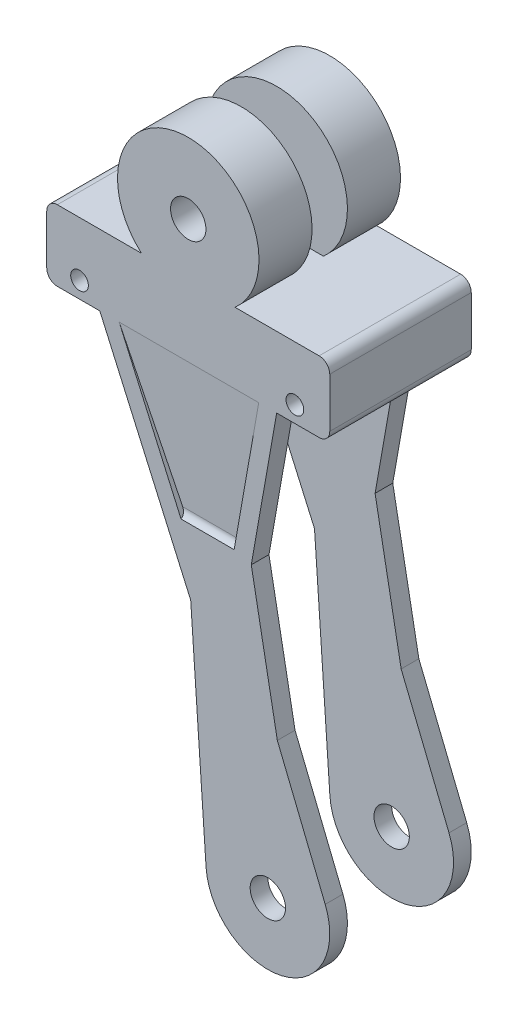
SolidWorks part; units mm, degrees
material "Titanio Ti-8Al-1Mo-1V"
ref_plane "Alzado" through (0, 0, 0) normal (0, 0, 1) x (1, 0, 0)
ref_plane "Planta" through (0, 0, 0) normal (0, 1, 0) x (1, 0, 0)
ref_plane "Vista lateral" through (0, 0, 0) normal (1, 0, 0) x (0, 0, -1)
other "Centro de masa"
sketch "Croquis1" plane through (0, 0, 0) normal (0, 0, 1) x (1, 0, 0)
  line L1 (-37, 0) -> (37, 0)
  line L2 (-40, -3) -> (-40, -17)
  line L3 (-37, -20) -> (37, -20)
  line L4 (40, -3) -> (40, -17)
  arc A0 (37, 0) -> (40, -3) centre (37, -3) cw
  arc A1 (37, -20) -> (40, -17) centre (37, -17) ccw
  arc A2 (-40, -17) -> (-37, -20) centre (-37, -17) ccw
  arc A3 (-37, 0) -> (-40, -3) centre (-37, -3) ccw
  point P6 (40, 0)
  point P9 (40, -20)
  point P14 (-40, 0)
  dimension "D3" = 3
  dimension "D1" = 80
  dimension "D2" = 20
extrude "Saliente-Extruir1" add sketch "Croquis1" along normal blind 40
sketch "Croquis2" plane through (0, 0, 40) normal (0, 0, 1) x (1, 0, 0)
  line L0 (0, -20) -> (22.5, -140) construction
  line L1 (-37, -20) -> (37, -20) construction
  line L2 (40, -17) -> (40, -3) construction
  line L3 (-25, -20) -> (0.6923, -77.9551)
  line L4 (0.6923, -77.9551) -> (5.0412, -141.2005)
  line L5 (-25, -20) -> (0, -20)
  line L6 (0, -20) -> (25, -20)
  line L7 (25.1863, -100.0643) -> (17.8148, -60.7494)
  line L8 (25.1863, -100.0643) -> (38.7168, -133.4223)
  line L9 (0.6923, -77.9551) -> (10.521, -76.1122) construction
  line L10 (17.8148, -60.7494) -> (25, -20)
  arc A0 (5.0412, -141.2005) -> (38.7168, -133.4223) centre (22.5, -140) ccw
  circle A1 centre (22.5, -140) radius 5
  line M7 (-37, -20) -> (37, -20)
  dimension "D2" = 35
  dimension "D8" = 10
  dimension "D1" = 120
  dimension "D3" = 25
  dimension "D4" = 10
  dimension "D5" = 40
  dimension "D6" = 10
  dimension "D7" = 80
extrude "Saliente-Extruir2" add sketch "Croquis2" against normal blind 5 contours L0 L3 L9 M7 | L0 A1 L9 L4 A0 L8 L7 L10 M7 region at (11.0487, -83.3083, 40)
extrude "Saliente-Extruir3" add sketch "Croquis2<4>" along normal blind 5 from surface starting at face at (0, -10, 0)
sketch "Croquis2<4>" plane through (0, 0, 40) normal (0, 0, 1) x (1, 0, 0) same geometry as "Croquis2"
ref_plane "Plano2" through (0, -1.4195, 40.6488) normal (0, -0.0349, 0.9994) x (1, 0, 0)
sketch "Croquis3" plane through (0, -1.4195, 40.6488) normal (0, -0.0349, 0.9994) x (1, 0, 0)
  line L0 (-19.5302, -18.5918) -> (19.9228, -18.5918)
  line L1 (19.9228, -18.5918) -> (12.9644, -58.0309)
  line L2 (12.9644, -58.0309) -> (-2.0356, -58.0309)
  line L3 (-2.0356, -58.0309) -> (-19.5302, -18.5918)
  line L4 (-25, -18.5918) -> (0.6923, -76.5117) construction
  line L5 (17.8148, -59.3164) -> (25, -18.5918) construction
  line L6 (25, -18.5918) -> (37, -18.5918) construction
  dimension "D1" = 5
  dimension "D2" = 5
  dimension "D3" = 15
extrude "Cortar-Extruir1" cut sketch "Croquis3" along normal through all
fillet "Redondeo5" radius 2 1 edges at (5.4644, -59.415, 38.6236)
ref_plane "Plano3" through (0, 0, 20) normal (0, 0, 1) x (1, 0, 0)
sketch "Croquis4" plane through (0, 0, 20) normal (0, 0, 1) x (1, 0, 0)
  line L0 (-36.4648, -15.405) -> (-36.4648, -20)
  line L1 (-37, -20) -> (-25, -20) construction
  line L2 (-25, -15.405) -> (-25, -20)
  line L3 (36.3387, -15.405) -> (36.3387, -20)
  line L4 (25, -20) -> (37, -20) construction
  line L5 (23.9618, -15.405) -> (23.9618, -20)
  line L6 (23.9618, -20) -> (36.3387, -20)
  line L7 (-36.4648, -20) -> (-25, -20)
  circle A0 centre (-30.7324, -15.405) radius 2.5
  circle A1 centre (30.1503, -15.405) radius 2.5
  arc A2 (36.3387, -15.405) -> (23.9618, -15.405) centre (30.1503, -15.405) ccw
  arc A3 (-25, -15.405) -> (-36.4648, -15.405) centre (-30.7324, -15.405) ccw
  dimension "D1" = 5
extrude "Cortar-Extruir2" cut sketch "Croquis4" against normal mid plane 10 contours L7 L2 A3 L0 | A2 L5 L6 L3
extrude "Cortar-Extruir3" cut sketch "Croquis4<4>" against normal through all both and the other way through all contours A0 | A1 region at (-30.7324, -15.405, 20)
sketch "Croquis4<4>" plane through (0, 0, 20) normal (0, 0, 1) x (1, 0, 0) same geometry as "Croquis4"
sketch "Croquis6" plane through (0, 0, 0) normal (0, 1, 0) x (1, 0, 0)
  line L0 (0, 0) -> (0, -40) construction
  line L1 (37, -40) -> (-37, -40) construction
  circle A0 centre (0, -20) radius 15
  dimension "D1" = 30
sketch "Croquis7" plane through (0, 0, 20) normal (0, 0, 1) x (1, 0, 0)
  line L0 (19.9228, -20) -> (-19.5302, -20) construction
  line L1 (0, 0) -> (0, 15) construction
  circle A0 centre (0, 15) radius 20
  circle A1 centre (0, 15) radius 5
  dimension "D1" = 35
  dimension "D2" = 40
  dimension "D3" = 10
extrude "Saliente-Extruir5" add sketch "Croquis7" against normal blind 15 from surface starting at face at (-28.2324, -15.405, 40)
extrude "Saliente-Extruir6" add sketch "Croquis7<2>" along normal blind 15 from surface starting at face at (-28.2324, -15.405, 0)
sketch "Croquis7<2>" plane through (0, 0, 20) normal (0, 0, 1) x (1, 0, 0) same geometry as "Croquis7"
